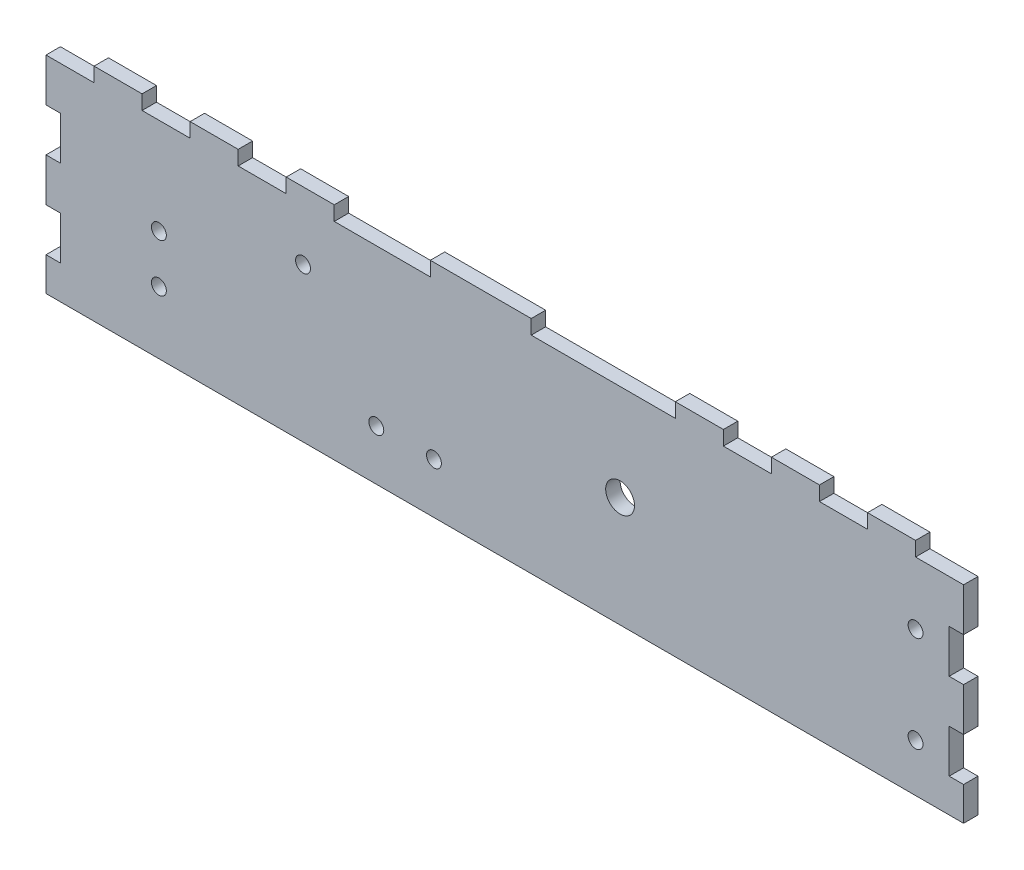
SolidWorks part; units mm, degrees
ref_plane "Front Plane" through (0, 0, 0) normal (0, 0, 1) x (1, 0, 0)
ref_plane "Top Plane" through (0, 0, 0) normal (0, 1, 0) x (1, 0, 0)
ref_plane "Right Plane" through (0, 0, 0) normal (1, 0, 0) x (0, 0, -1)
sketch "Sketch1" plane through (0, 0, 0) normal (0, 0, 1) x (1, 0, 0)
  line L4 (0, 0) -> (191, 0)
  line L5 (191, 0) -> (191, 46)
  line L6 (191, 46) -> (0, 46)
  line L7 (0, 46) -> (0, 0)
  line L8 (0, 0) -> (191, 0)
  line L9 (191, 0) -> (191, 46)
  line L10 (191, 46) -> (0, 46)
  line L11 (0, 46) -> (0, 0)
  circle A0 centre (181, 30) radius 1.55 construction
  circle A1 centre (181, 10) radius 1.55 construction
  circle A2 centre (181, 30) radius 1.55
  circle A3 centre (181, 10) radius 1.55
  dimension "D1" = 0
extrude "Boss-Extrude1" add sketch "Sketch1" along normal blind 3
sketch "Sketch3" plane through (0, 0, 3) normal (0, 0, 1) x (1, 0, 0)
  line L0 (119.5, 46) -> (119.5, 0) construction
  line L1 (119.5, 46) -> (119.5, 0)
  point P2 (119.5, 23)
ref_point "MountPoint-Sus"
sketch "Sketch4" plane through (0, 0, 0) normal (0, 0, -1) x (-1, 0, 0)
  line L0 (-10, 43) -> (-10, 46) construction
  line L1 (-10, 46) -> (0, 46) construction
  line L2 (0, 46) -> (0, 43) construction
  line L3 (0, 43) -> (-10, 43) construction
  line L4 (-30, 43) -> (-30, 46) construction
  line L5 (-30, 46) -> (-20, 46) construction
  line L6 (-20, 46) -> (-20, 43) construction
  line L7 (-20, 43) -> (-30, 43) construction
  line L8 (-50, 43) -> (-50, 46) construction
  line L9 (-50, 46) -> (-40, 46) construction
  line L10 (-40, 46) -> (-40, 43) construction
  line L11 (-40, 43) -> (-50, 43) construction
  line L12 (-60, 43) -> (-80, 43) construction
  line L13 (-80, 43) -> (-80, 46) construction
  line L14 (-80, 46) -> (-60, 46) construction
  line L15 (-60, 46) -> (-60, 43) construction
  line L16 (-131, 43) -> (-131, 46) construction
  line L17 (-131, 46) -> (-101, 46) construction
  line L18 (-101, 46) -> (-101, 43) construction
  line L19 (-101, 43) -> (-131, 43) construction
  line L20 (-151, 43) -> (-151, 46) construction
  line L21 (-151, 46) -> (-141, 46) construction
  line L22 (-141, 46) -> (-141, 43) construction
  line L23 (-141, 43) -> (-151, 43) construction
  line L24 (-171, 43) -> (-171, 46) construction
  line L25 (-171, 46) -> (-161, 46) construction
  line L26 (-161, 46) -> (-161, 43) construction
  line L27 (-161, 43) -> (-171, 43) construction
  line L28 (-191, 46) -> (-181, 46) construction
  line L29 (-181, 46) -> (-181, 43) construction
  line L30 (-181, 43) -> (-191, 43) construction
  line L31 (-191, 43) -> (-191, 46) construction
  line L32 (-10, 43) -> (-10, 46)
  line L33 (-10, 46) -> (0, 46)
  line L34 (0, 46) -> (0, 43)
  line L35 (0, 43) -> (-10, 43)
  line L36 (-30, 43) -> (-30, 46)
  line L37 (-30, 46) -> (-20, 46)
  line L38 (-20, 46) -> (-20, 43)
  line L39 (-20, 43) -> (-30, 43)
  line L40 (-50, 43) -> (-50, 46)
  line L41 (-50, 46) -> (-40, 46)
  line L42 (-40, 46) -> (-40, 43)
  line L43 (-40, 43) -> (-50, 43)
  line L44 (-60, 43) -> (-80, 43)
  line L45 (-80, 43) -> (-80, 46)
  line L46 (-80, 46) -> (-60, 46)
  line L47 (-60, 46) -> (-60, 43)
  line L48 (-131, 43) -> (-131, 46)
  line L49 (-131, 46) -> (-101, 46)
  line L50 (-101, 46) -> (-101, 43)
  line L51 (-101, 43) -> (-131, 43)
  line L52 (-151, 43) -> (-151, 46)
  line L53 (-151, 46) -> (-141, 46)
  line L54 (-141, 46) -> (-141, 43)
  line L55 (-141, 43) -> (-151, 43)
  line L56 (-171, 43) -> (-171, 46)
  line L57 (-171, 46) -> (-161, 46)
  line L58 (-161, 46) -> (-161, 43)
  line L59 (-161, 43) -> (-171, 43)
  line L60 (-191, 46) -> (-181, 46)
  line L61 (-181, 46) -> (-181, 43)
  line L62 (-181, 43) -> (-191, 43)
  line L63 (-191, 43) -> (-191, 46)
extrude "Cut-Extrude1" cut sketch "Sketch4" against normal up to next
sketch "Sketch5" plane through (0, 0, 0) normal (0, 0, -1) x (-1, 0, 0)
  line L4 (0, 34) -> (-3, 34)
  line L5 (0, 25) -> (0, 34)
  line L6 (-3, 25) -> (0, 25)
  line L7 (-3, 34) -> (-3, 25)
  line L8 (0, 34) -> (-3, 34)
  line L9 (0, 25) -> (0, 34)
  line L10 (-3, 25) -> (0, 25)
  line L11 (-3, 34) -> (-3, 25)
  line L12 (-3, 7) -> (0, 7)
  line L13 (0, 7) -> (0, 16)
  line L14 (0, 16) -> (-3, 16)
  line L15 (-3, 16) -> (-3, 7)
  line L16 (-3, 7) -> (0, 7)
  line L17 (0, 7) -> (0, 16)
  line L18 (0, 16) -> (-3, 16)
  line L19 (-3, 16) -> (-3, 7)
  dimension "D1" = 0
  dimension "D2" = 0
extrude "Cut-Extrude2" cut sketch "Sketch5" against normal up to next
sketch "Sketch6" plane through (0, 0, 0) normal (0, 0, -1) x (-1, 0, 0)
  line L0 (-188, 25) -> (-188, 34) construction
  line L1 (-188, 34) -> (-191, 34) construction
  line L2 (-191, 25) -> (-188, 25) construction
  line L3 (-188, 16) -> (-191, 16) construction
  line L4 (-188, 7) -> (-188, 16) construction
  line L5 (-191, 7) -> (-188, 7) construction
  line L6 (-188, 25) -> (-188, 34)
  line L7 (-188, 34) -> (-191, 34)
  line L8 (-191, 25) -> (-188, 25)
  line L9 (-188, 16) -> (-191, 16)
  line L10 (-188, 7) -> (-188, 16)
  line L11 (-191, 7) -> (-188, 7)
  line L40 (-3, 7) -> (-3, 16)
  line L41 (-3, 16) -> (0, 16)
  line L42 (0, 16) -> (0, 25)
  line L43 (0, 25) -> (-3, 25)
  line L44 (-3, 25) -> (-3, 34)
  line L45 (-3, 34) -> (0, 34)
  line L46 (0, 34) -> (0, 43)
  line L47 (0, 43) -> (-10, 43)
  line L48 (-10, 43) -> (-10, 46)
  line L49 (-10, 46) -> (-20, 46)
  line L50 (-20, 46) -> (-20, 43)
  line L51 (-20, 43) -> (-30, 43)
  line L52 (-30, 43) -> (-30, 46)
  line L53 (-30, 46) -> (-40, 46)
  line L54 (-40, 46) -> (-40, 43)
  line L55 (-40, 43) -> (-50, 43)
  line L56 (-50, 43) -> (-50, 46)
  line L57 (-50, 46) -> (-60, 46)
  line L58 (-60, 46) -> (-60, 43)
  line L59 (-60, 43) -> (-80, 43)
  line L60 (-80, 43) -> (-80, 46)
  line L61 (-80, 46) -> (-101, 46)
  line L62 (-101, 46) -> (-101, 43)
  line L63 (-101, 43) -> (-131, 43)
  line L64 (-131, 43) -> (-131, 46)
  line L65 (-131, 46) -> (-141, 46)
  line L66 (-141, 46) -> (-141, 43)
  line L67 (-141, 43) -> (-151, 43)
  line L68 (-151, 43) -> (-151, 46)
  line L69 (-151, 46) -> (-161, 46)
  line L70 (-161, 46) -> (-161, 43)
  line L71 (-161, 43) -> (-171, 43)
  line L72 (-171, 43) -> (-171, 46)
  line L73 (-171, 46) -> (-181, 46)
  line L74 (-181, 46) -> (-181, 43)
  line L75 (-181, 43) -> (-191, 43)
  line L76 (-191, 43) -> (-191, 0)
  line L77 (-191, 0) -> (0, 0)
  line L78 (0, 0) -> (0, 7)
  line L79 (0, 7) -> (-3, 7)
  line L80 (-3, 7) -> (-3, 16)
  line L81 (-3, 16) -> (0, 16)
  line L82 (0, 16) -> (0, 25)
  line L83 (0, 25) -> (-3, 25)
  line L84 (-3, 25) -> (-3, 34)
  line L85 (-3, 34) -> (0, 34)
  line L86 (0, 34) -> (0, 43)
  line L87 (0, 43) -> (-10, 43)
  line L88 (-10, 43) -> (-10, 46)
  line L89 (-10, 46) -> (-20, 46)
  line L90 (-20, 46) -> (-20, 43)
  line L91 (-20, 43) -> (-30, 43)
  line L92 (-30, 43) -> (-30, 46)
  line L93 (-30, 46) -> (-40, 46)
  line L94 (-40, 46) -> (-40, 43)
  line L95 (-40, 43) -> (-50, 43)
  line L96 (-50, 43) -> (-50, 46)
  line L97 (-50, 46) -> (-60, 46)
  line L98 (-60, 46) -> (-60, 43)
  line L99 (-60, 43) -> (-80, 43)
  line L100 (-80, 43) -> (-80, 46)
  line L101 (-80, 46) -> (-101, 46)
  line L102 (-101, 46) -> (-101, 43)
  line L103 (-101, 43) -> (-131, 43)
  line L104 (-131, 43) -> (-131, 46)
  line L105 (-131, 46) -> (-141, 46)
  line L106 (-141, 46) -> (-141, 43)
  line L107 (-141, 43) -> (-151, 43)
  line L108 (-151, 43) -> (-151, 46)
  line L109 (-151, 46) -> (-161, 46)
  line L110 (-161, 46) -> (-161, 43)
  line L111 (-161, 43) -> (-171, 43)
  line L112 (-171, 43) -> (-171, 46)
  line L113 (-171, 46) -> (-181, 46)
  line L114 (-181, 46) -> (-181, 43)
  line L115 (-181, 43) -> (-191, 43)
  line L116 (-191, 43) -> (-191, 0)
  line L117 (-191, 0) -> (0, 0)
  line L118 (0, 0) -> (0, 7)
  line L119 (0, 7) -> (-3, 7)
  line M78 (-191, 43) -> (-191, 0)
  dimension "D1" = 0
extrude "Cut-Extrude3" cut sketch "Sketch6" against normal up to next contours L8 L6 L7 M78 | L11 L10 L9 M78 region at (189.5, 29.5, 0) region at (189.5, 11.5, 0)
sketch "Sketch7" plane through (0, 0, 3) normal (0, 0, 1) x (1, 0, 0)
  circle A0 centre (119.5, 23) radius 3
  point P0 (119.5, 23)
  dimension "D1" = 6
extrude "Cut-Extrude4" cut sketch "Sketch7" against normal up to next
sketch "Sketch8" plane through (0, 0, 3) normal (0, 0, 1) x (1, 0, 0)
  circle A0 centre (23.5, 13) radius 1.55 construction
  circle A1 centre (23.5, 23) radius 1.55 construction
  circle A2 centre (53.5, 32) radius 1.55 construction
  circle A3 centre (68.7574, 10.5) radius 1.55 construction
  circle A4 centre (80.7574, 10.5) radius 1.55 construction
  circle A5 centre (23.5, 13) radius 1.55
  circle A6 centre (23.5, 23) radius 1.55
  circle A7 centre (53.5, 32) radius 1.55
  circle A8 centre (68.7574, 10.5) radius 1.55
  circle A9 centre (80.7574, 10.5) radius 1.55
extrude "Cut-Extrude5" cut sketch "Sketch8" against normal up to next
